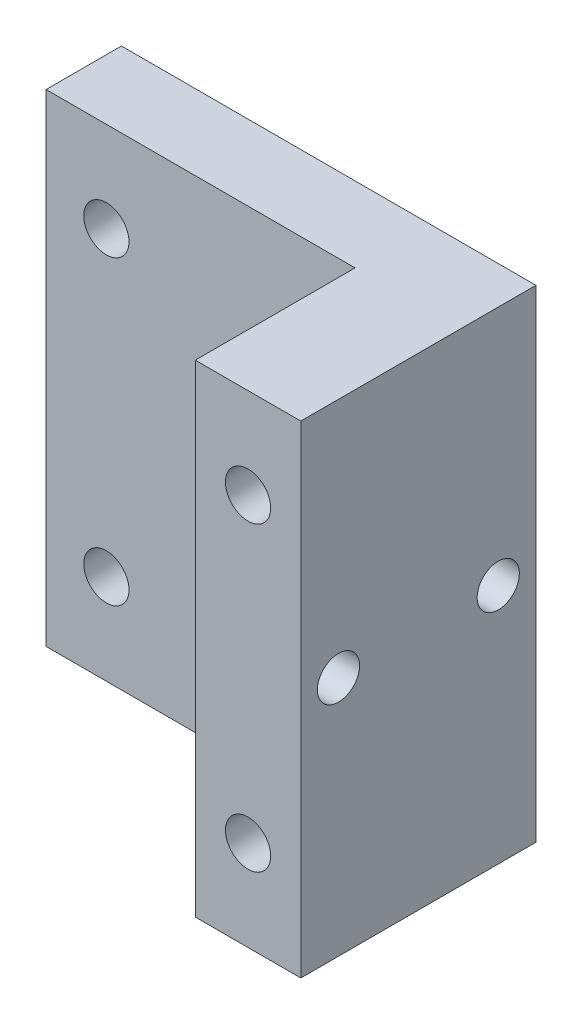
SolidWorks part; units mm, degrees
ref_plane "Front Plane" through (0, 0, 0) normal (0, 0, 1) x (1, 0, 0)
ref_plane "Top Plane" through (0, 0, 0) normal (0, 1, 0) x (1, 0, 0)
ref_plane "Right Plane" through (0, 0, 0) normal (1, 0, 0) x (0, 0, -1)
sketch "Sketch1" plane through (0, 0, 0) normal (0, 0, 1) x (1, 0, 0)
  line L1 (374.1154, -314.2464) -> (346.6154, -314.2464)
  line L2 (374.1154, -314.2464) -> (374.1154, -346.2464)
  line L3 (374.1154, -346.2464) -> (346.6154, -346.2464)
  line L4 (346.6154, -314.2464) -> (346.6154, -346.2464)
  line L8 (374.1154, -314.2464) -> (367.1154, -314.2464)
  line L9 (374.1154, -314.2464) -> (374.1154, -346.2464)
  line L10 (374.1154, -346.2464) -> (367.1154, -346.2464)
  line L11 (367.1154, -314.2464) -> (367.1154, -346.2464)
  circle A1 centre (370.6154, -340.2464) radius 1.5
  circle A2 centre (370.6154, -320.2464) radius 1.5
  circle A4 centre (350.6154, -320.2464) radius 1.5
  circle A5 centre (350.6154, -340.2464) radius 1.5
  point P25 (355.7872, -306.8254)
  dimension "D4" = 3
  dimension "D5" = 3
  dimension "D6" = 3
  dimension "D7" = 3
  dimension "D8" = 20
  dimension "D9" = 20
  dimension "D10" = 20
  dimension "D3" = 7
  dimension "D11" = 0
extrude "Boss-Extrude1" add sketch "Sketch1" along normal blind 5 contours L1 L11 L3 L2 A2 A1 | L11 L1 L4 L3 region at (370.6154, -330.2464, 0) region at (357.0031, -330.2464, 0)
extrude "Boss-Extrude2" add sketch "Sketch1<3>" along normal blind 15.6 contours L1 L11 L3 L2 A2 A1 region at (370.6154, -330.2464, 0)
sketch "Sketch1<3>" plane through (0, 0, 0) normal (0, 0, 1) x (1, 0, 0) same geometry as "Sketch1"
sketch "Sketch2" plane through (374.1154, 0, 0) normal (1, 0, 0) x (0, 0, -1)
  line L0 (-15.6001, -330.2464) -> (0, -330.2464) construction
  line L1 (0, -314.2464) -> (0, -346.2464) construction
  arc A0 (-12.711, -327.7769) -> (-12.711, -332.716) centre (-13.1001, -330.2464) ccw construction
  circle A1 centre (-13.1001, -330.2464) radius 1.4
  circle A2 centre (-2.5001, -330.2464) radius 1.4
  dimension "D1" = 2.8
  dimension "D2" = 2.8
extrude "Cut-Extrude1" cut sketch "Sketch2" against normal through all
sketch "Sketch3" plane through (346.6154, 0, 0) normal (-1, 0, 0) x (0, 0, 1)
  line L1 (5.4922, -331.992) -> (5.5079, -328.528)
  line L2 (5.5079, -328.528) -> (2.5157, -326.7824)
  line L3 (2.5157, -326.7824) -> (-0.4921, -328.5008)
  line L4 (-0.4921, -328.5008) -> (-0.5077, -331.9649)
  line L5 (-0.5077, -331.9649) -> (2.4844, -333.7105)
  line L6 (2.4844, -333.7105) -> (5.4922, -331.992)
  circle A0 centre (2.5001, -330.2464) radius 3 construction
  dimension "D1" = 6
